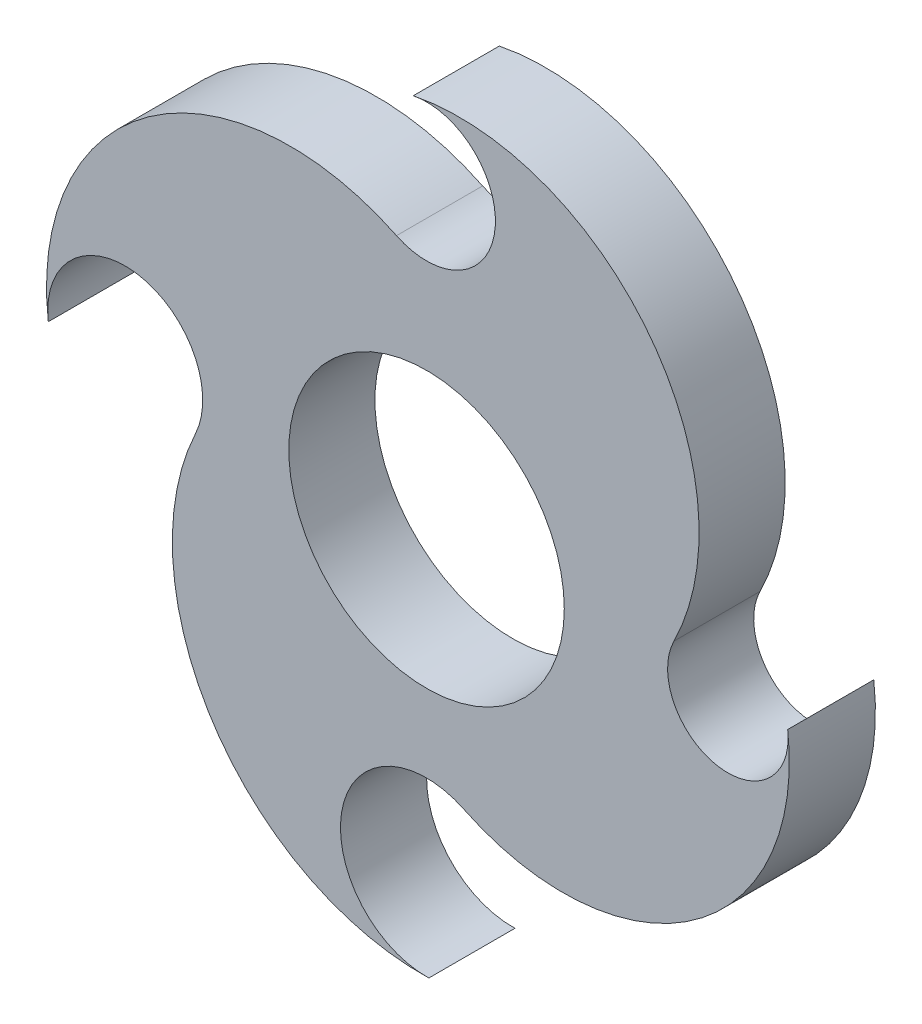
SolidWorks part; units mm, degrees
ref_plane "前基準面" through (0, 0, 0) normal (0, 0, 1) x (1, 0, 0)
ref_plane "上基準面" through (0, 0, 0) normal (0, 1, 0) x (1, 0, 0)
ref_plane "右基準面" through (0, 0, 0) normal (1, 0, 0) x (0, 0, -1)
sketch "草圖1" plane through (0, 0, 0) normal (0, 0, 1) x (1, 0, 0)
  circle A0 centre (0, 0) radius 16
  circle A1 centre (0, 0) radius 35 construction
  circle A2 centre (0, 35) radius 8 construction
  circle A7 centre (35, 0) radius 7 construction
  circle A8 centre (0, -35) radius 10 construction
  circle A9 centre (-35, 0) radius 9 construction
  arc A10 (0.2694, -44.9964) -> (4.3598, -26.0005) centre (0, -35) cw
  arc A11 (-43.9346, -1.0827) -> (-26.8351, -3.786) centre (-35, 0) cw
  arc A12 (-1.5415, 42.8501) -> (-3.4879, 27.8004) centre (0, 35) cw
  arc A14 (-26.8351, -3.786) -> (0.2694, -44.9964) centre (-0.5122, -15.9918) ccw
  arc A15 (4.3598, -26.0005) -> (41.9492, 0.8421) centre (15.8305, -2.3229) ccw
  arc A17 (-3.4879, 27.8004) -> (-43.9346, -1.0827) centre (-15.8305, 2.3229) ccw
  arc A18 (41.9492, 0.8421) -> (28.7348, 3.1221) centre (35, 0) cw
  arc A19 (28.7348, 3.1221) -> (-1.5415, 42.8501) centre (3.8219, 15.5368) ccw
  dimension "D1" = 32
  dimension "D2" = 70
  dimension "D3" = 16
  dimension "D5" = 14
  dimension "D4" = 18
  dimension "D6" = 20
extrude "填料-伸長1" add sketch "草圖1" along normal blind 10
